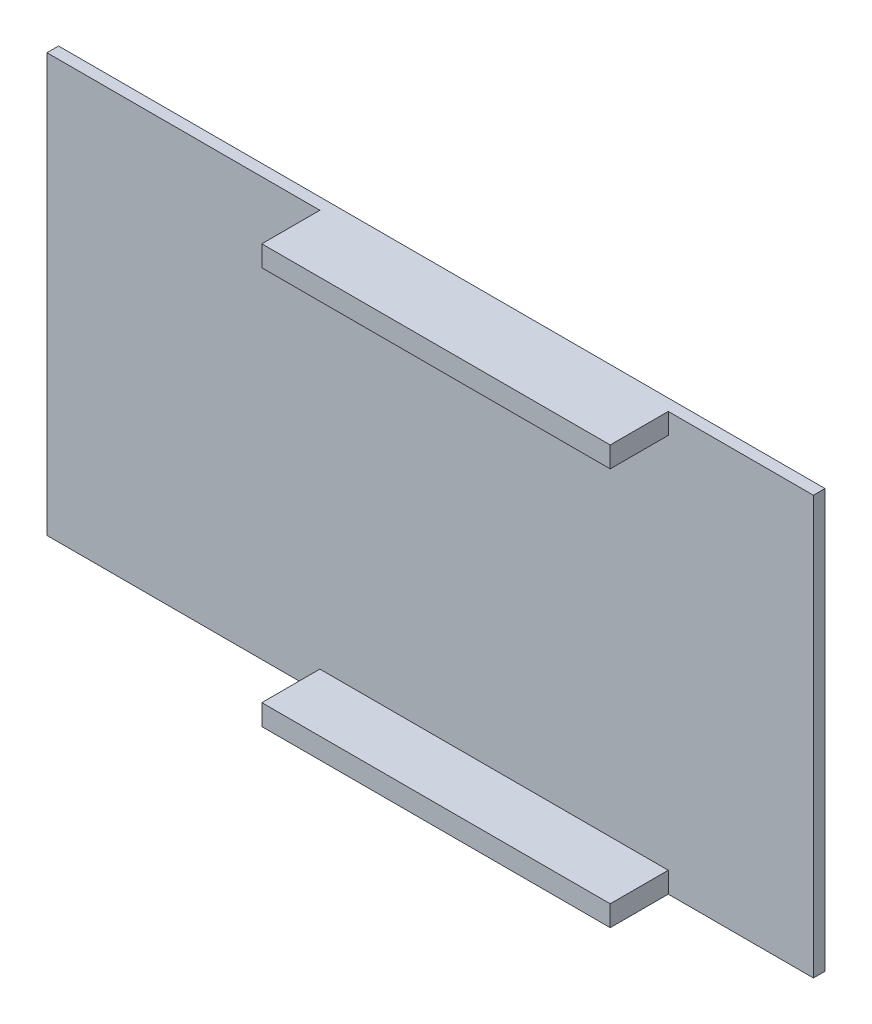
SolidWorks part; units mm, degrees
ref_plane "Front Plane" through (0, 0, 0) normal (0, 0, 1) x (1, 0, 0)
ref_plane "Top Plane" through (0, 0, 0) normal (0, 1, 0) x (1, 0, 0)
ref_plane "Right Plane" through (0, 0, 0) normal (1, 0, 0) x (0, 0, -1)
sketch "Sketch1" plane through (0, 0, 0) normal (0, 0, 1) x (1, 0, 0)
  line L1 (-66, -36) -> (66, -36)
  line L2 (-66, -36) -> (-66, 36)
  line L3 (-66, 36) -> (66, 36)
  line L4 (66, -36) -> (66, 36)
  line L5 (-66, -36) -> (66, 36) construction
  line L6 (-66, 36) -> (66, -36) construction
  point P0 (0, 0)
  dimension "D1" = 72
  dimension "D2" = 132
extrude "Boss-Extrude1" add sketch "Sketch1" along normal blind 2
sketch "Sketch2" plane through (0, 0, 2) normal (0, 0, 1) x (1, 0, 0)
  line L0 (-19, 36) -> (41, 36)
  line L1 (-19, 36) -> (-19, 32.4298)
  line L2 (41, 36) -> (41, 32.4298)
  line L3 (-19, 32.4298) -> (41, 32.4298)
  line L4 (66, 36) -> (-66, 36) construction
  line L5 (66, -36) -> (66, 36) construction
  dimension "D1" = 60
  dimension "D2" = 25
extrude "Boss-Extrude2" add sketch "Sketch2" along normal blind 10
ref_point "Point1"
ref_axis "Axis1" through (-66, 0, 1) along (-1, 0, 0)
ref_plane "Plane1" through (0, 0, 0) normal (0, 1, 0) x (-1, 0, 0)
mirror "Mirror1" about plane through (0, 0, 0) normal (0, 1, 0) of "Boss-Extrude2"
